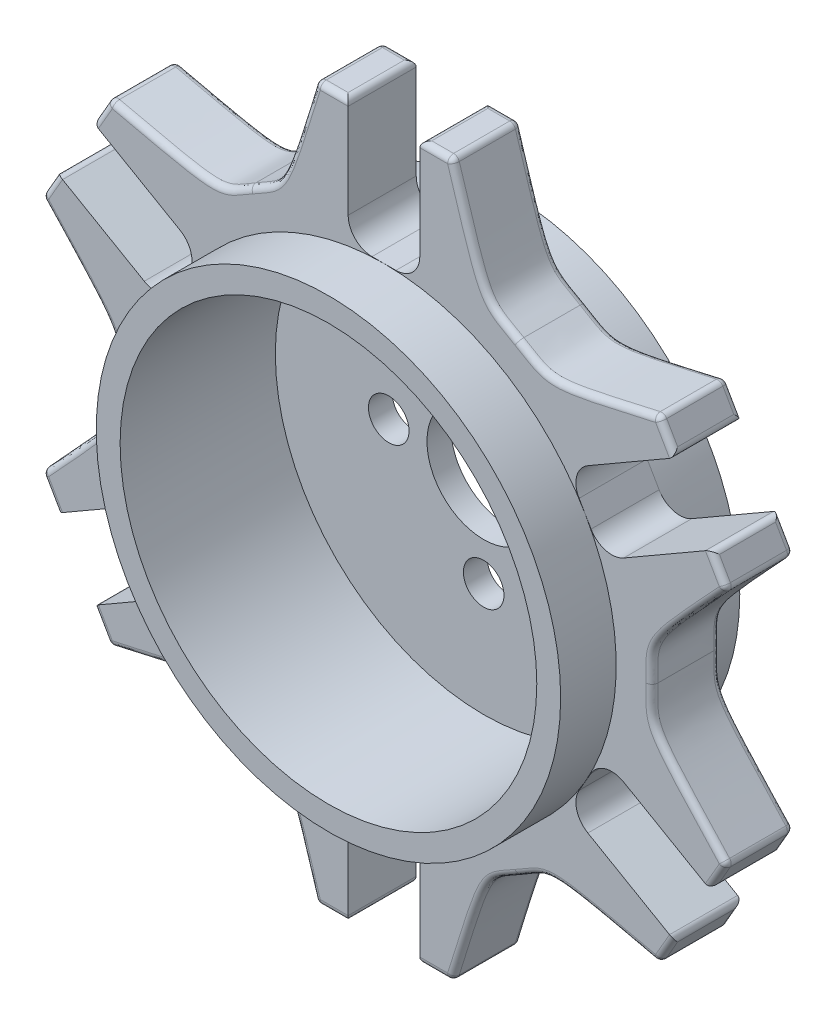
SolidWorks part; units mm, degrees
ref_plane "前基準面" through (0, 0, 0) normal (0, 0, 1) x (1, 0, 0)
ref_plane "上基準面" through (0, 0, 0) normal (0, 1, 0) x (1, 0, 0)
ref_plane "右基準面" through (0, 0, 0) normal (1, 0, 0) x (0, 0, -1)
sketch "草圖1" plane through (0, 0, 0) normal (0, 0, 1) x (1, 0, 0)
  circle A0 centre (0, 0) radius 19.45
  dimension "D1" = 38.9
extrude "伸長1" add sketch "草圖1" along normal blind 15
shell "薄殼1" thickness 2 removed face at (19.45, 0, 15)
sketch "草圖2" plane through (0, 0, 0) normal (0, 0, -1) x (-1, 0, 0)
  line L0 (0, 0) -> (0, 19.45) construction
  line L1 (0, 0) -> (19.45, 0) construction
  line L2 (0, 0) -> (0, -19.45) construction
  line L3 (0, 0) -> (-19.45, 0) construction
  line L4 (7.95, 0) -> (0, 7.95) construction
  line L5 (0, 7.95) -> (-7.95, 0) construction
  line L6 (-7.95, 0) -> (0, -7.95) construction
  line L7 (0, -7.95) -> (7.95, 0) construction
  circle A0 centre (0, 0) radius 4.75
  circle A1 centre (0, 0) radius 19.45 construction
  circle A2 centre (0, 7.95) radius 1.7
  circle A3 centre (7.95, 0) radius 1.7
  circle A4 centre (0, -7.95) radius 1.7
  circle A5 centre (-7.95, 0) radius 1.7
  dimension "D1" = 9.5
  dimension "D2" = 3.4
  dimension "D3" = 7.95
  dimension "D4" = 7.95
extrude "伸長2" cut sketch "草圖2" against normal blind 15
ref_plane "平面1" through (0, 0, 7.5) normal (0, 0, -1) x (-1, 0, 0)
sketch "草圖3" plane through (0, 0, 7.5) normal (0, 0, -1) x (-1, 0, 0)
  line L0 (0, 0) -> (0, 30) construction
  line L1 (0, 0) -> (-15, 25.9808) construction
  line L2 (0, 30) -> (-15, 25.9808) construction
  line L3 (0, 19.45) -> (-1, 19.45)
  line L4 (-3, 21.45) -> (-3, 29.85)
  line L5 (-3, 29.85) -> (-5.7, 29.85)
  line L6 (-5.7, 29.85) -> (-9.725, 16.8442) construction
  line L7 (-11.225, 19.4423) -> (-9.725, 16.8442) construction
  line L8 (-23.0009, 19.8613) -> (-9.725, 16.8442) construction
  line L9 (-25.9808, 15) -> (-15, 25.9808) construction
  line L10 (-24.3509, 17.5231) -> (-23.0009, 19.8613)
  line L11 (-17.0762, 13.3231) -> (-24.3509, 17.5231)
  line L12 (-16.8442, 9.725) -> (-16.3442, 10.591)
  circle A0 centre (0, 0) radius 19.45 construction
  arc A1 (0, 19.45) -> (-16.8442, 9.725) centre (0, 0) ccw
  arc A2 (-1, 19.45) -> (-3, 21.45) centre (-1, 21.45) cw
  arc A3 (-16.3442, 10.591) -> (-17.0762, 13.3231) centre (-18.0762, 11.591) ccw
  spline S0 degree 3 poles (-5.7, 29.85) (-8.6564, 20.297) (-8.3382, 21.1089) (-11.225, 19.4423) knots 0 0 0 0 0.52225 0.52225 0.52225 0.52225
  spline S1 degree 3 poles (-23.0009, 19.8613) (-13.2495, 17.6452) (-14.1118, 17.7756) (-11.225, 19.4423) knots 0 0 0 0 0.52225 0.52225 0.52225 0.52225
  dimension "D3" = 2
  dimension "D7" = 30
  dimension "D8" = 10
  dimension "D1" = 30
  dimension "D2" = 30
  dimension "D4" = 2.7
  dimension "D5" = 8.4
  dimension "D6" = 3
  dimension "D9" = 3
extrude "伸長4" add sketch "草圖3" along normal blind 2.85 and the other way blind 2.85
fillet "圓角2" radius 0.5 12 edges at (4.35, 29.85, 10.35) (3, 29.85, 7.5) (4.35, 29.85, 4.65) (5.7, 29.85, 7.5) (23.6759, 18.6922, 10.35) (23.0009, 19.8613, 7.5) (23.6759, 18.6922, 4.65) (24.3509, 17.5231, 7.5)
pattern_circular "環狀複製排列8" count 6 over 360 about axis through (0, 0, 15) along (0, 0, -1) of "伸長4", "圓角2"
